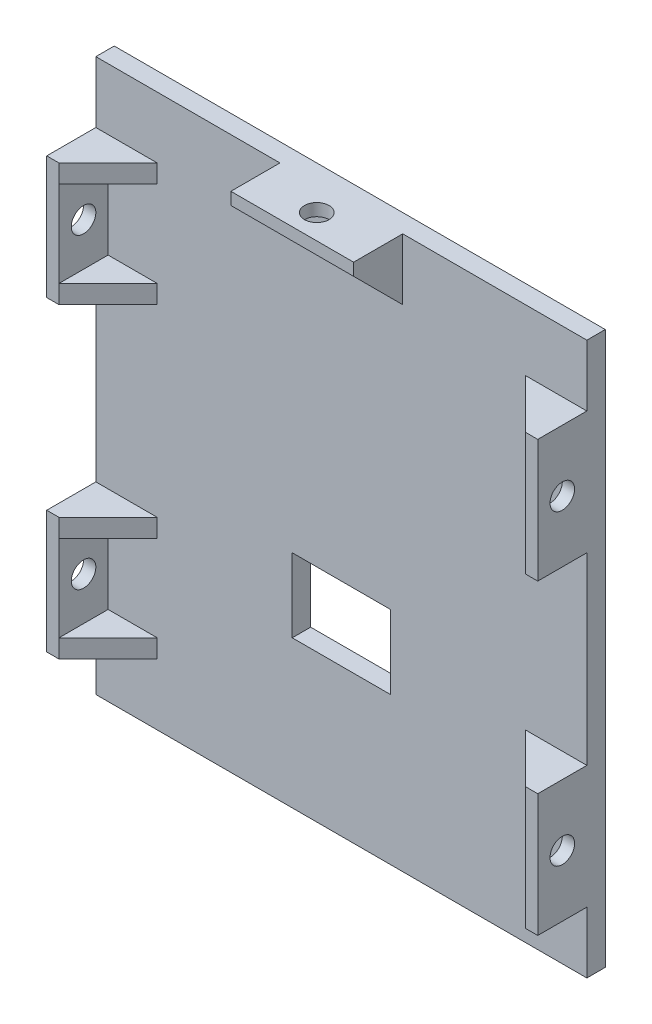
SolidWorks part; units mm, degrees
ref_plane "Front Plane" through (0, 0, 0) normal (0, 0, 1) x (1, 0, 0)
ref_plane "Top Plane" through (0, 0, 0) normal (0, 1, 0) x (1, 0, 0)
ref_plane "Right Plane" through (0, 0, 0) normal (1, 0, 0) x (0, 0, -1)
sketch "Sketch1" plane through (0, 0, 0) normal (0, 0, 1) x (1, 0, 0)
  line L1 (0, 0) -> (80, 0)
  line L2 (0, 0) -> (0, 90)
  line L3 (0, 90) -> (80, 90)
  line L4 (80, 0) -> (80, 90)
  dimension "D1" = 90
  dimension "D2" = 80
extrude "Boss-Extrude1" add sketch "Sketch1" along normal blind 3
sketch "Sketch2" plane through (0, 0, 3) normal (0, 0, 1) x (1, 0, 0)
  line L0 (0, 90) -> (0, 0) construction
  line L1 (0, 80) -> (10, 80)
  line L2 (0, 80) -> (0, 60)
  line L3 (0, 60) -> (10, 60)
  line L4 (10, 80) -> (10, 77)
  line L5 (80, 90) -> (0, 90) construction
  line L6 (10, 77) -> (2, 77)
  line L7 (2, 77) -> (2, 63)
  line L8 (2, 63) -> (10, 63)
  line L9 (10, 63) -> (10, 60)
  dimension "D1" = 10
  dimension "D2" = 20
  dimension "D3" = 3
  dimension "D4" = 3
  dimension "D5" = 2
  dimension "D6" = 10
extrude "Boss-Extrude2" add sketch "Sketch2" along normal blind 8
sketch "Sketch3" plane through (0, 80, 0) normal (0, 1, 0) x (1, 0, 0)
  line L0 (10, -3) -> (2, -11)
  line L1 (10, -11) -> (0, -11) construction
  line L2 (2, -11) -> (10, -11)
  line L3 (10, -11) -> (10, -3)
  line L4 (10, -3) -> (0, -3) construction
  dimension "D1" = 45
extrude "Cut-Extrude1" cut sketch "Sketch3" against normal through all
sketch "Sketch6" plane through (2, 0, 0) normal (1, 0, 0) x (0, 0, -1)
  line L0 (-11, 63) -> (-11, 77) construction
  line L1 (-11, 80) -> (-3, 80) construction
  circle A0 centre (-7, 70) radius 2
  dimension "D1" = 4
  dimension "D2" = 10
extrude "Cut-Extrude3" cut sketch "Sketch6" against normal blind 25
ref_plane "Plane1" through (40, 0, 0) normal (1, 0, 0) x (0, 0, -1)
ref_plane "Plane3" through (0, 45, 0) normal (0, -1, 0) x (-1, 0, 0)
mirror "Mirror4" about plane through (40, 0, 0) normal (1, 0, 0) of "Cut-Extrude3", "Boss-Extrude2", "Cut-Extrude1"
mirror "Mirror5" about plane through (0, 45, 0) normal (0, -1, 0) of "Boss-Extrude2", "Cut-Extrude1", "Mirror4"
sketch "Sketch4" plane through (0, 0, 3) normal (0, 0, 1) x (1, 0, 0)
  line L0 (80, 90) -> (0, 90) construction
  line L1 (30, 90) -> (50, 90)
  line L2 (30, 90) -> (30, 80)
  line L3 (30, 80) -> (33, 80)
  line L4 (50, 90) -> (50, 80)
  line L5 (40, -1.65) -> (40, 1.65) construction
  line L6 (33, 80) -> (33, 88)
  line L7 (33, 88) -> (47, 88)
  line L8 (47, 88) -> (47, 80)
  line L9 (47, 80) -> (50, 80)
  dimension "D1" = 20
  dimension "D2" = 10
  dimension "D3" = 10
  dimension "D4" = 3
  dimension "D5" = 3
  dimension "D6" = 2
extrude "Boss-Extrude3" add sketch "Sketch4" along normal blind 8
sketch "Sketch5" plane through (30, 0, 0) normal (-1, 0, 0) x (0, 0, 1)
  line L0 (3, 80) -> (11, 88)
  line L1 (11, 90) -> (11, 80) construction
  line L2 (11, 88) -> (11, 80)
  line L3 (11, 80) -> (3, 80)
  line L4 (3, 90) -> (3, 80) construction
  dimension "D1" = 45
extrude "Cut-Extrude2" cut sketch "Sketch5" against normal blind 25
sketch "Sketch7" plane through (0, 88, 0) normal (0, -1, 0) x (1, 0, 0)
  line L0 (33, 11) -> (47, 11) construction
  line L1 (50, 11) -> (50, 3) construction
  circle A0 centre (40, 7) radius 2
  dimension "D1" = 4
  dimension "D2" = 4
  dimension "D3" = 10
extrude "Cut-Extrude4" cut sketch "Sketch7" against normal blind 25
sketch "Sketch8" plane through (0, 0, 3) normal (0, 0, 1) x (1, 0, 0)
  line L0 (40, 45) -> (40, 30)
  line L1 (-1.65, 45) -> (1.65, 45) construction
  line L2 (40, -1.65) -> (40, 1.65) construction
  line L4 (32, 36) -> (48, 36)
  line L5 (32, 36) -> (32, 24)
  line L6 (32, 24) -> (48, 24)
  line L7 (48, 36) -> (48, 24)
  line L8 (32, 36) -> (48, 24) construction
  line L9 (32, 24) -> (48, 36) construction
  dimension "D1" = 15
  dimension "D2" = 12
  dimension "D3" = 16
extrude "Cut-Extrude5" cut sketch "Sketch8" against normal blind 10 contours L7 L4 L5 L6 region at (36, 35.8, 3)
equation "\"D4@Sketch2\"=\"D3@Sketch2\""
